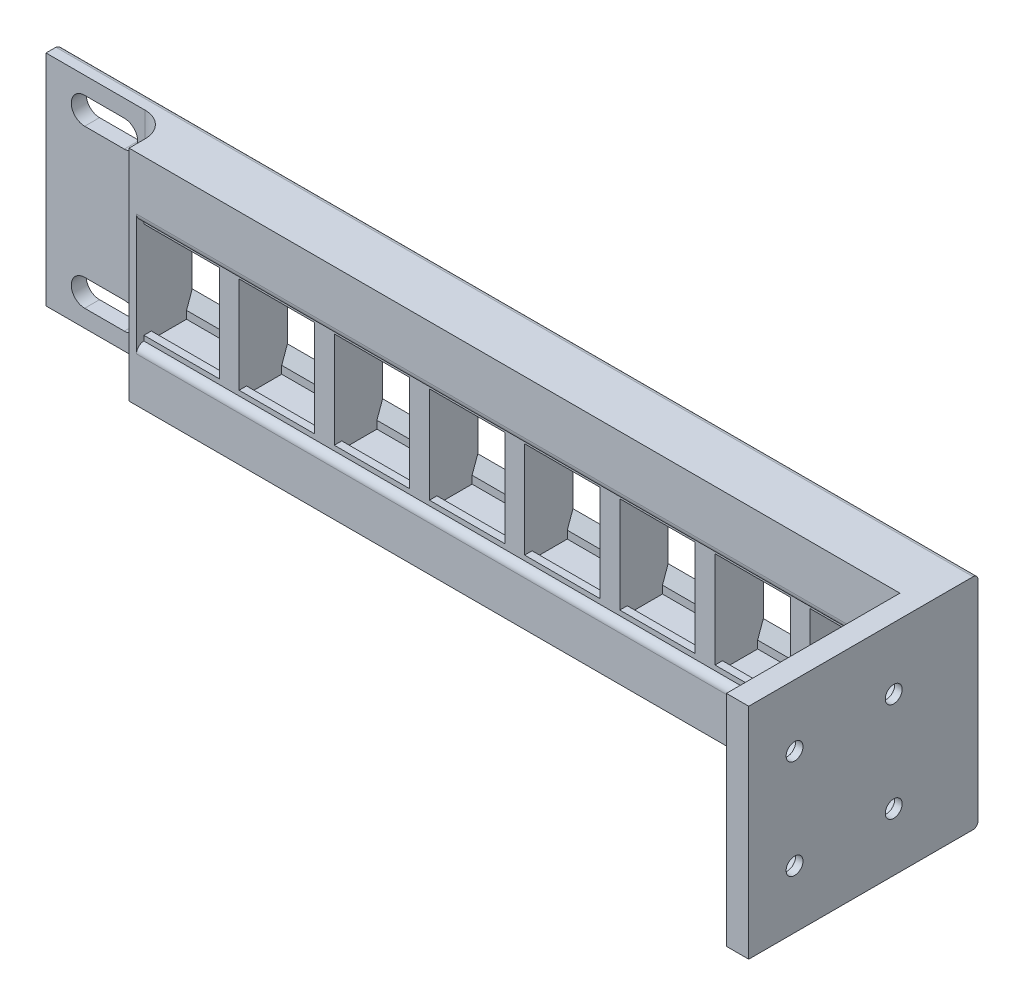
SolidWorks part; units mm, degrees
ref_plane "Front Plane" through (0, 0, 0) normal (0, 0, 1) x (1, 0, 0)
ref_plane "Top Plane" through (0, 0, 0) normal (0, 1, 0) x (1, 0, 0)
ref_plane "Right Plane" through (0, 0, 0) normal (1, 0, 0) x (0, 0, -1)
sketch "Sketch1" plane through (0, 0, 0) normal (0, 0, 1) x (1, 0, 0)
  line L1 (-92.5, 22.1) -> (92.5, 22.1)
  line L2 (-92.5, 22.1) -> (-92.5, -22.1)
  line L3 (-92.5, -22.1) -> (92.5, -22.1)
  line L4 (92.5, 22.1) -> (92.5, -22.1)
  line L5 (-92.5, 22.1) -> (92.5, -22.1) construction
  line L6 (-92.5, -22.1) -> (92.5, 22.1) construction
  point P0 (0, 0)
  dimension "D1" = 185
  dimension "D2" = 44.2
extrude "Boss-Extrude1" add sketch "Sketch1" along normal blind 11.25
sketch "Sketch2" plane through (0, 0, 11.25) normal (0, 0, 1) x (1, 0, 0)
  line L0 (-92.5, -22.1) -> (92.5, -22.1) construction
  line L1 (-92.5, 22.1) -> (-67.5, 22.1)
  line L2 (-92.5, 22.1) -> (-92.5, -22.1)
  line L3 (-92.5, -22.1) -> (-67.5, -22.1)
  line L4 (-67.5, 22.1) -> (-67.5, -22.1)
  dimension "D1" = 25
extrude "Cut-Extrude1" cut sketch "Sketch2" against normal offset from surface (8.25 mm away) 3 up to face at (0, 0, 0)
fillet "Fillet1" radius 5 1 edges at (-67.5, 0, 3)
ref_plane "Plane1" through (-66, 0, 0) normal (-1, 0, 0) x (0, 0, 1)
sketch "Sketch3" plane through (-66, 0, 0) normal (-1, 0, 0) x (0, 0, 1)
  line L0 (0, 8.85) -> (1.15, 8.85)
  line L1 (0, 22.1) -> (0, -22.1) construction
  line L2 (1.15, 8.85) -> (1.15, 10.35)
  line L3 (1.15, 10.35) -> (8.25, 10.35)
  line L4 (8.25, 10.35) -> (8.25, 8.85)
  line L5 (8.25, 8.85) -> (11.25, 8.85)
  line L6 (11.25, 8.85) -> (11.25, -10.6)
  line L7 (11.25, -10.6) -> (8.25, -10.6)
  line L8 (8.25, -10.6) -> (8.25, -12.1)
  line L9 (8.25, -12.1) -> (1.15, -12.1)
  line L10 (1.15, -12.1) -> (1.15, -10.5457)
  line L11 (1.15, -10.5457) -> (0, -7.36)
  line L12 (0, -7.36) -> (0, 8.85)
  line L13 (3, -22.1) -> (0, -22.1) construction
  dimension "D1" = 1.15
  dimension "D2" = 1.5
  dimension "D3" = 7.1
  dimension "D4" = 3
  dimension "D5" = 1.5
  dimension "D6" = 19.45
  dimension "D7" = 3
  dimension "D8" = 1.5
  dimension "D9" = 7.1
  dimension "D10" = 16.21
  dimension "D11" = 10
extrude "Cut-Extrude2" cut sketch "Sketch3" against normal blind 15.2
pattern_linear "LPattern1" count 8 spacing 19.2 along (1, 0, 0) of "Cut-Extrude2"
sketch "Sketch4" plane through (0, 0, 11.25) normal (0, 0, 1) x (1, 0, 0)
  line L0 (-67.5, -22.1) -> (92.5, -22.1) construction
  line L1 (92.5, 22.1) -> (88, 22.1)
  line L2 (92.5, 22.1) -> (92.5, -22.1)
  line L3 (92.5, -22.1) -> (88, -22.1)
  line L4 (88, 22.1) -> (88, -22.1)
  dimension "D1" = 4.5
extrude "Boss-Extrude2" add sketch "Sketch4" along normal blind 35
sketch "Sketch9" plane through (88, 0, 0) normal (-1, 0, 0) x (0, 0, 1)
  line L0 (0, -22.1) -> (0, 22.1) construction
  line L1 (46.25, 22.1) -> (11.25, 22.1) construction
  point P0 (17, 9.6)
  point P2 (37, 9.6)
  point P4 (17, -10.4)
  point P6 (37, -10.4)
  dimension "D1" = 17
  dimension "D2" = 20
  dimension "D3" = 20
  dimension "D4" = 12.5
hole_wizard "CBORE for M3 SHCS1" positions "Sketch9" profile "Sketch8" counterbore size "M3" standard "ANSI Metric"
sketch "Sketch8" plane through (88, 9.6, 17) normal (0, 1, 0) x (0, 0, 1)
  line L0 (0, 0) -> (0, 11.1215)
  line L1 (0, 11.1215) -> (1.7, 10.1)
  line L2 (1.7, 10.1) -> (1.7, 3)
  line L3 (1.7, 3) -> (3.25, 3)
  line L4 (3.25, 3) -> (3.25, 0)
  line L5 (3.25, 0) -> (0, 0)
  line L10 (0, 11.1215) -> (-1.7, 10.1) construction
  line L11 (0, -6.35) -> (0, 107.95) construction
  dimension "Hole Dia." = 3.4
  dimension "Hole Depth" = 10.1
  dimension "C'Bore Dia." = 6.5
  dimension "C'Bore Depth" = 3
  dimension "Drill Angle" = 118
sketch "Sketch10" plane through (0, 0, 0) normal (0, 0, -1) x (-1, 0, 0)
  line L0 (76.7, 15.9) -> (84.7, 15.9) construction
  line L1 (76.7, 18.6) -> (84.7, 18.6)
  line L2 (76.7, 13.2) -> (84.7, 13.2)
  line L6 (76.7, -15.9) -> (84.7, -15.9) construction
  line L7 (76.7, -13.2) -> (84.7, -13.2)
  line L8 (76.7, -18.6) -> (84.7, -18.6)
  line L9 (67.5, -22.1) -> (67.5, 22.1) construction
  arc A0 (76.7, 18.6) -> (76.7, 13.2) centre (76.7, 15.9) ccw
  arc A1 (84.7, 13.2) -> (84.7, 18.6) centre (84.7, 15.9) ccw
  arc A2 (76.7, -13.2) -> (76.7, -18.6) centre (76.7, -15.9) ccw
  arc A3 (84.7, -18.6) -> (84.7, -13.2) centre (84.7, -15.9) ccw
  point P2 (80.7, 15.9)
  point P7 (74, 15.9)
  point P14 (80.7, -15.9)
  dimension "D3" = 6.5
  dimension "D1" = 5.4
  dimension "D2" = 8
  dimension "D4" = 15.9
  dimension "D6" = 15.9
  dimension "D5" = 2
extrude "Cut-Extrude3" cut sketch "Sketch10" against normal blind 35
fillet "Fillet2" radius 1 16 edges at (76, -10.6, 11.25) (76, 8.85, 11.25) (56.8, 8.85, 11.25) (56.8, -10.6, 11.25) (37.6, -10.6, 11.25) (37.6, 8.85, 11.25) (18.4, -10.6, 11.25) (18.4, 8.85, 11.25) (-0.8, 8.85, 11.25) (-0.8, -10.6, 11.25) (-20, -10.6, 11.25) (-20, 8.85, 11.25) (-39.2, 8.85, 11.25) (-39.2, -10.6, 11.25) (-58.4, -10.6, 11.25) (-58.4, 8.85, 11.25)
fillet "Fillet3" radius 1 3 edges at (-92.5, 0, 0) (0, -22.1, 0) (0, 22.1, 0)
sketch "Sketch11" plane through (-66, 0, 0) normal (1, 0, 0) x (0, 0, -1)
  line L1 (-11.25, 9.85) -> (-9.75, 9.85)
  line L2 (-11.25, 9.85) -> (-11.25, -11.6)
  line L3 (-11.25, -11.6) -> (-9.75, -11.6)
  line L4 (-9.75, 9.85) -> (-9.75, -11.6)
  dimension "D1" = 1.5
extrude "Cut-Extrude4" cut sketch "Sketch11" along normal up to surface (154 mm away) up to face at (88, 9.6, 20.25)
fillet "Fillet4" radius 1.5 2 edges at (11, -11.6, 11.25) (11, 9.85, 11.25)
ref_plane "Plane2" through (-49.8, 0, 0) normal (-1, 0, 0) x (0, 0, 1)
ref_plane "Plane3" through (-30.6, 0, 0) normal (-1, 0, 0) x (0, 0, 1)
split "Split1" [suppressed] bodies to split 108
